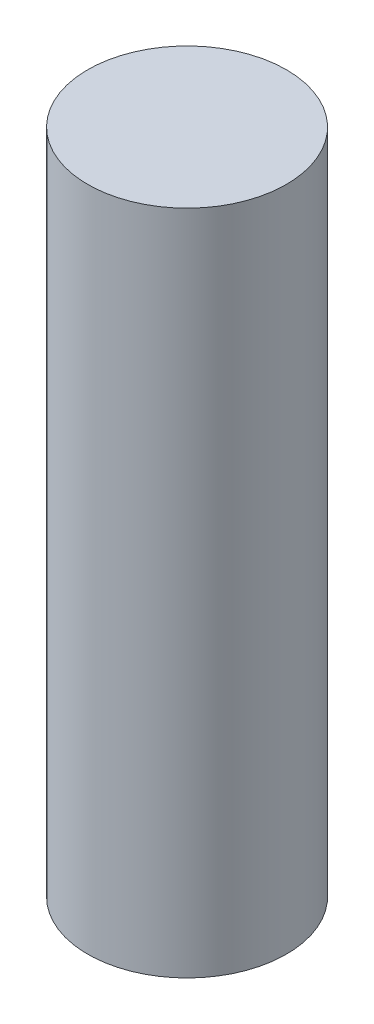
SolidWorks part; units mm, degrees
ref_plane "Front Plane" through (0, 0, 0) normal (0, 0, 1) x (1, 0, 0)
ref_plane "Top Plane" through (0, 0, 0) normal (0, 1, 0) x (1, 0, 0)
ref_plane "Right Plane" through (0, 0, 0) normal (1, 0, 0) x (0, 0, -1)
sketch "Sketch1" plane through (0, 0, 0) normal (0, 1, 0) x (1, 0, 0)
  circle A0 centre (0, 0) radius 3.937
  dimension "D1" = 7.874
extrude "Boss-Extrude1" add sketch "Sketch1" along normal blind 26.416
